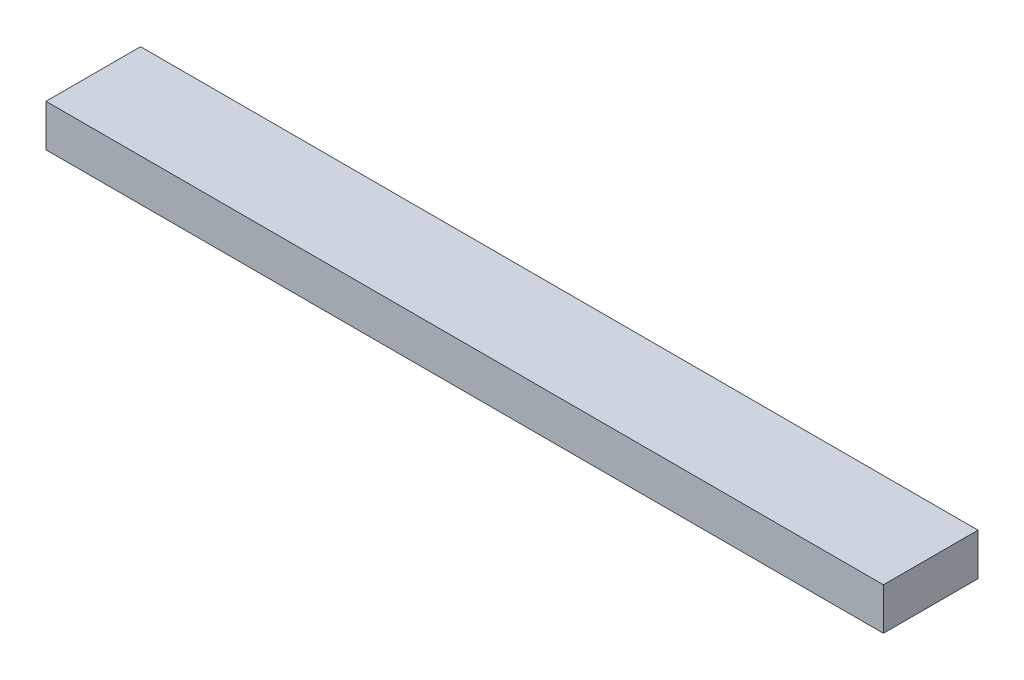
SolidWorks part; units mm, degrees
material "MDF"
ref_plane "Front Plane" through (0, 0, 0) normal (0, 0, 1) x (1, 0, 0)
ref_plane "Top Plane" through (0, 0, 0) normal (0, 1, 0) x (1, 0, 0)
ref_plane "Right Plane" through (0, 0, 0) normal (1, 0, 0) x (0, 0, -1)
sketch "Sketch1" plane through (0, 0, 0) normal (0, 0, 1) x (1, 0, 0)
  line L0 (0, -336.2045) -> (0, 336.2045) construction
  line L1 (-126.4888, -311.15) -> (126.4888, -311.15)
  line L2 (-126.4888, -311.15) -> (-126.4888, -298.45)
  line L3 (-126.4888, -298.45) -> (126.4888, -298.45)
  line L4 (0, -311.15) -> (0, -298.45) construction
  line L5 (126.4888, -311.15) -> (126.4888, -298.45)
  dimension "D1" = 12.7
extrude "Boss-Extrude1" add sketch "Sketch1" along normal up to surface (28.575 mm away)
